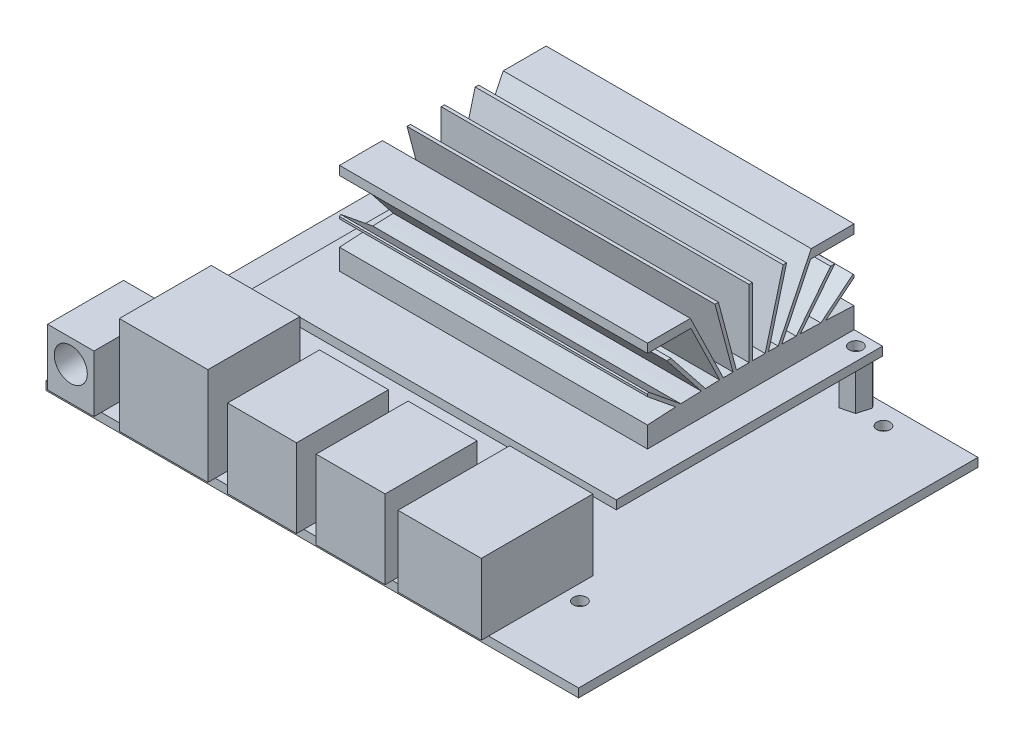
SolidWorks part; units mm, degrees
ref_plane "Front" through (0, 0, 0) normal (0, 0, 1) x (1, 0, 0)
ref_plane "Top" through (0, 0, 0) normal (0, 1, 0) x (1, 0, 0)
ref_plane "Right" through (0, 0, 0) normal (1, 0, 0) x (0, 0, -1)
sketch "Sketch1" plane through (0, 0, 0) normal (0, 1, 0) x (1, 0, 0)
  line L0 (16.3322, 73.66) -> (13.7922, 73.66) construction
  line L1 (0, 0) -> (101.6, 0)
  line L2 (0, 0) -> (0, 76.2)
  line L3 (0, 76.2) -> (101.6, 76.2)
  line L4 (101.6, 0) -> (101.6, 76.2)
  line L5 (13.7922, 76.2) -> (83.3882, 76.2)
  line L6 (13.7922, 76.2) -> (13.7922, 25.4)
  line L7 (13.7922, 25.4) -> (83.3882, 25.4)
  line L8 (83.3882, 76.2) -> (83.3882, 25.4)
  line L10 (16.3322, 76.2) -> (16.3322, 73.66) construction
  line L11 (80.8482, 73.66) -> (83.3882, 73.66) construction
  circle A0 centre (3.81, 72.39) radius 1.27
  circle A1 centre (87.376, 72.39) radius 1.27
  circle A2 centre (87.376, 14.478) radius 1.27
  circle A3 centre (3.81, 14.478) radius 1.27
  circle A4 centre (16.3322, 73.66) radius 1.27
  circle A5 centre (80.8482, 73.66) radius 1.27
  point P13 (3.81, 71.12)
  point P14 (3.81, 15.748)
  point P15 (3.81, 73.66)
  point P18 (2.54, 72.39)
  dimension "D4" = 2.54
  dimension "D11" = 2.54
  dimension "D1" = 101.6
  dimension "D2" = 76.2
  dimension "D3" = 2.54
  dimension "D5" = 55.372
  dimension "D6" = 83.566
  dimension "D7" = 2.54
  dimension "D8" = 69.596
  dimension "D9" = 50.8
  dimension "D10" = 13.7922
extrude "Boss-Extrude1" add sketch "Sketch1" along normal blind 1.651 contours L3 L8 L7 L6 L2 L1 L4 A3 A2 A1 A0 | L8 L3 L6 L7 region at (1.27, 0, -38.1) region at (48.5902, 0, -50.7343)
ref_plane "Plane1" through (0, 9.271, 0) normal (0, 1, 0) x (1, 0, 0)
extrude "Boss-Extrude2" add sketch "Sketch1<3>" along normal blind 1.651 from surface separate body contours L8 L3 L6 L7 region at (48.5902, 0, -50.7343) starting at plane "Plane1"
sketch "Sketch1<3>" plane through (0, 0, 0) normal (0, 1, 0) x (1, 0, 0) same geometry as "Sketch1"
sketch "Sketch3" plane through (0, 1.651, 0) normal (0, 1, 0) x (1, 0, 0)
  line L0 (83.3882, 76.2) -> (13.7922, 76.2) construction
  line L1 (79.0077, 75.5522) -> (78.2893, 73.0122)
  line L2 (78.2893, 73.0122) -> (80.1298, 71.12)
  line L3 (80.1298, 71.12) -> (82.6887, 71.7678)
  line L4 (82.6887, 71.7678) -> (83.4071, 74.3078)
  line L5 (83.4071, 74.3078) -> (81.5666, 76.2)
  line L6 (81.5666, 76.2) -> (79.0077, 75.5522)
  line L7 (17.0506, 76.2) -> (14.4917, 75.5522)
  line L8 (14.4917, 75.5522) -> (13.7733, 73.0122)
  line L9 (13.7733, 73.0122) -> (15.6138, 71.12)
  line L10 (15.6138, 71.12) -> (18.1727, 71.7678)
  line L11 (18.1727, 71.7678) -> (18.8911, 74.3078)
  line L12 (18.8911, 74.3078) -> (17.0506, 76.2)
  circle A0 centre (80.8482, 73.66) radius 2.286 construction
  circle A1 centre (16.3322, 73.66) radius 2.286 construction
  dimension "D1" = 4.572
extrude "Boss-Extrude3" add sketch "Sketch3" along normal up to surface (7.62 mm away) up to face at (48.5902, 9.271, -50.8)
ref_plane "Plane2" through (48.5902, 0, 0) normal (1, 0, 0) x (0, 0, -1)
sketch "Sketch4" plane through (48.5902, 0, 0) normal (1, 0, 0) x (0, 0, -1)
  line L0 (36.7792, 14.8844) -> (36.7792, 19.9644)
  line L1 (76.2, 10.922) -> (36.7792, 10.922)
  line L2 (76.2, 10.922) -> (76.2, 14.8844)
  line L3 (76.2, 14.8844) -> (36.7792, 14.8844) construction
  line L4 (36.7792, 10.922) -> (36.7792, 14.8844)
  line L5 (36.7792, 19.9644) -> (76.2, 19.9644) construction
  line L6 (76.2, 19.9644) -> (76.2, 14.8844)
  line L7 (36.7792, 19.9644) -> (36.7792, 28.4099)
  line L8 (36.7792, 28.4099) -> (76.2, 28.4099)
  line L9 (76.2, 28.4099) -> (76.2, 19.9644)
  line L10 (56.4896, 3.9438) -> (56.4896, 29.3438)
  line L11 (67.3292, 26.9981) -> (68.0145, 28.4099)
  line L13 (72.5129, 23.652) -> (71.7027, 23.652)
  line L14 (56.4896, 3.9438) -> (63.0137, 28.4916) construction
  line L16 (67.5827, 26.7934) -> (56.4896, 3.9438) construction
  line L17 (56.4896, 3.9438) -> (72.2653, 23.8508) construction
  line L19 (76.2, 19.9644) -> (56.4896, 3.9438) construction
  line L20 (76.2, 26.7208) -> (67.9004, 26.7208)
  line L21 (76.2, 28.4099) -> (76.2, 26.7208)
  line L22 (76.2, 27.5653) -> (67.9575, 27.5653) construction
  line L23 (67.9575, 27.5653) -> (67.5827, 26.7934) construction
  line L24 (36.5805, -11.8292) -> (75.9982, 20.2095)
  line L25 (36.5805, -11.8292) -> (36.981, -12.322)
  line L26 (75.9982, 20.2095) -> (76.3987, 19.7168)
  line L27 (36.981, -12.322) -> (76.3987, 19.7168)
  line L28 (36.5805, -11.8292) -> (76.3987, 19.7168) construction
  line L29 (75.9982, 20.2095) -> (36.981, -12.322) construction
  line L30 (40.4663, -15.7644) -> (72.0152, 24.0464)
  line L31 (40.4663, -15.7644) -> (40.964, -16.1588)
  line L32 (72.0152, 24.0464) -> (72.5129, 23.652) construction
  line L33 (40.964, -16.1588) -> (72.5129, 23.652)
  line L34 (40.4663, -15.7644) -> (72.5129, 23.652) construction
  line L35 (72.0152, 24.0464) -> (40.964, -16.1588) construction
  line L36 (45.0788, -18.8332) -> (67.3292, 26.9981)
  line L37 (45.0788, -18.8332) -> (45.65, -19.1106)
  line L38 (67.3292, 26.9981) -> (67.9004, 26.7208) construction
  line L39 (45.65, -19.1106) -> (67.9004, 26.7208)
  line L40 (45.0788, -18.8332) -> (67.9004, 26.7208) construction
  line L41 (67.3292, 26.9981) -> (45.65, -19.1106) construction
  line L42 (49.6591, -20.5206) -> (62.7064, 28.5712)
  line L43 (49.6591, -20.5206) -> (50.2728, -20.6837)
  line L44 (62.7064, 28.5712) -> (63.3201, 28.4081) construction
  line L45 (50.2728, -20.6837) -> (63.3201, 28.4081)
  line L46 (49.6591, -20.5206) -> (63.3201, 28.4081) construction
  line L47 (62.7064, 28.5712) -> (50.2728, -20.6837) construction
  line L48 (56.1721, -21.4542) -> (56.1721, 29.3418) construction
  line L49 (56.1721, -21.4542) -> (56.8071, -21.4542)
  line L50 (56.1721, 29.3418) -> (56.8071, 29.3418)
  line L51 (56.8071, -21.4542) -> (56.8071, 29.3418)
  line L52 (56.1721, -21.4542) -> (56.8071, 29.3418) construction
  line L53 (56.1721, 29.3418) -> (56.8071, -21.4542) construction
  line L54 (63.3201, 28.4081) -> (63.7281, 29.9435)
  line L55 (63.7281, 29.9435) -> (63.1144, 30.1066)
  line L56 (63.1144, 30.1066) -> (62.7064, 28.5712)
  arc A0 (76.2, 14.8844) -> (36.7792, 14.8844) centre (56.4896, -303.4623) ccw
  arc A1 (76.2, 19.9644) -> (36.7792, 19.9644) centre (56.4896, 3.9438) ccw construction
  point P9 (56.4896, 15.494)
  point P13 (62.992, 28.4099)
  point P24 (56.4896, 28.4099)
  dimension "D7" = 25.4
  dimension "D1" = 3.9624
  dimension "D2" = 4.572
  dimension "D3" = 39.4208
  dimension "D4" = 17.4879
  dimension "D5" = 5.08
  dimension "D6" = 0.635
  dimension "D8" = 6.5024
  dimension "D9" = 1.6891
  dimension "D10" = 12.5
  dimension "D11" = 12.5
extrude "Boss-Extrude4" add sketch "Sketch4" along normal mid plane 58.75 separate body contours L51 A0 L10 L1 | L42 A0 L51 L1 | L45 A0 L42 L1 | L36 A0 L45 L1 | L39 A0 L36 L1 | L30 A0 L39 L1 | L33 A0 L30 L1 | L24 A0 L33 L1 | L27 A0 L24 L1 | L2 A0 L27 L1 | A0 L27 L6 L26 L24 | A0 L33 L13 L30 | A0 L39 L20 L9 L8 L11 L36 | A0 L45 L54 L8 L42 | A0 L51 L8 L10 region at (48.5902, 13.208, -56.6483) region at (48.5902, 21.9519, -56.6484) region at (48.5902, 13.4603, -57.748) region at (48.5902, 13.2006, -58.9497) region at (48.5902, 21.9446, -61.2737) region at (48.5902, 13.4729, -60.0556) region at (48.5902, 13.1835, -60.9752) region at (48.5902, 21.1397, -64.7011) region at (48.5902, 13.4143, -62.5107) region at (48.5902, 13.1437, -63.7799) region at (48.5902, 19.5087, -68.8245) region at (48.5902, 13.3292, -65.9186) region at (48.5902, 13.0577, -67.7018) region at (48.5902, 17.5621, -73.2335) region at (48.5902, 12.7659, -72.0013)
mirror "Mirror2" about plane through (77.9652, 0, -56.4896) normal (0, 0, 1) of bodies 104
sketch "Sketch5" plane through (0, 1.651, 0) normal (0, 1, 0) x (1, 0, 0)
  line L0 (0, -1.4) -> (101.6, -1.4) construction
  line L1 (0, 0) -> (101.6, 0) construction
  line L2 (84.44, 19.9) -> (68.54, 19.9)
  line L3 (84.44, 19.9) -> (84.44, -1.4)
  line L4 (84.44, -1.4) -> (68.54, -1.4)
  line L5 (68.54, 19.9) -> (68.54, -1.4)
  line L6 (66.09, 16.14) -> (52.94, 16.14)
  line L7 (66.09, 16.14) -> (66.09, -1.4)
  line L8 (66.09, -1.4) -> (52.94, -1.4)
  line L9 (52.94, 16.14) -> (52.94, -1.4)
  line L10 (49.19, 16.14) -> (36.04, 16.14)
  line L11 (49.19, 16.14) -> (49.19, -1.4)
  line L12 (49.19, -1.4) -> (36.04, -1.4)
  line L13 (36.04, 16.14) -> (36.04, -1.4)
  line L14 (32.29, -1.4) -> (15.39, -1.4)
  line L15 (32.29, -1.4) -> (32.29, 16.14)
  line L16 (32.29, 16.14) -> (15.39, 16.14)
  line L17 (15.39, -1.4) -> (15.39, 16.14)
  line L18 (10.55, -1.4) -> (1.7, -1.4)
  line L19 (10.55, -1.4) -> (10.55, 13.1)
  line L20 (10.55, 13.1) -> (1.7, 13.1)
  line L21 (1.7, -1.4) -> (1.7, 13.1)
  line L22 (101.6, 0) -> (101.6, 76.2) construction
  line L23 (0, 0) -> (0, 76.2) construction
  line M35 (0, 0) -> (101.6, 0)
  dimension "D1" = 1.4
  dimension "D2" = 16.9
  dimension "D3" = 13.15
  dimension "D4" = 15.9
  dimension "D5" = 1.7
  dimension "D6" = 4.84
  dimension "D7" = 3.75
  dimension "D8" = 3.75
  dimension "D9" = 2.45
  dimension "D10" = 21.3
  dimension "D11" = 8.85
  dimension "D12" = 17.54
  dimension "D13" = 14.5
extrude "Boss-Extrude5" add sketch "Sketch5" along normal blind 13.53 contours L2 L5 L3 M35 | L5 L4 L3 M35 region at (76.49, 1.651, -9.95) region at (76.49, 1.651, 0.7)
extrude "Boss-Extrude6" add sketch "Sketch5<3>" along normal blind 15 contours L6 L9 L7 M35 | L10 L13 L11 M35 | L13 L12 L11 M35 | L9 L8 L7 M35 region at (42.615, 1.651, 0.7) region at (42.615, 1.651, -8.07) region at (59.515, 1.651, 0.7) region at (59.515, 1.651, -8.07)
sketch "Sketch5<3>" plane through (0, 1.651, 0) normal (0, 1, 0) x (1, 0, 0) same geometry as "Sketch5"
extrude "Boss-Extrude7" add sketch "Sketch5<4>" along normal blind 18.63 contours L17 L15 L16 M35 | L17 L14 L15 M35 region at (23.84, 1.651, 0.7) region at (23.84, 1.651, -8.07)
sketch "Sketch5<4>" plane through (0, 1.651, 0) normal (0, 1, 0) x (1, 0, 0) same geometry as "Sketch5"
extrude "Boss-Extrude8" add sketch "Sketch5<5>" along normal blind 10.84 contours L21 L19 L20 M35 | L21 L18 L19 M35 region at (6.125, 1.651, 0.7) region at (6.125, 1.651, -6.55)
sketch "Sketch5<5>" plane through (0, 1.651, 0) normal (0, 1, 0) x (1, 0, 0) same geometry as "Sketch5"
sketch "Sketch6" plane through (0, 0, 1.4) normal (0, 0, 1) x (1, 0, 0)
  line L3 (1.7, 8.066) -> (2.97, 8.066) construction
  line L5 (1.7, 12.491) -> (1.7, 1.651) construction
  line L8 (10.55, 12.491) -> (1.7, 12.491) construction
  line L9 (6.125, 12.491) -> (6.125, 11.221) construction
  line L11 (10.55, 12.491) -> (10.55, 1.651) construction
  line L12 (10.55, 8.066) -> (9.28, 8.066) construction
  circle A0 centre (6.125, 8.066) radius 3.155
  point P4 (2.97, 8.066)
  point P15 (9.28, 8.066)
  point P16 (0, 0)
  dimension "D1" = 1.27
extrude "Cut-Extrude1" cut sketch "Sketch6" against normal blind 6.35
